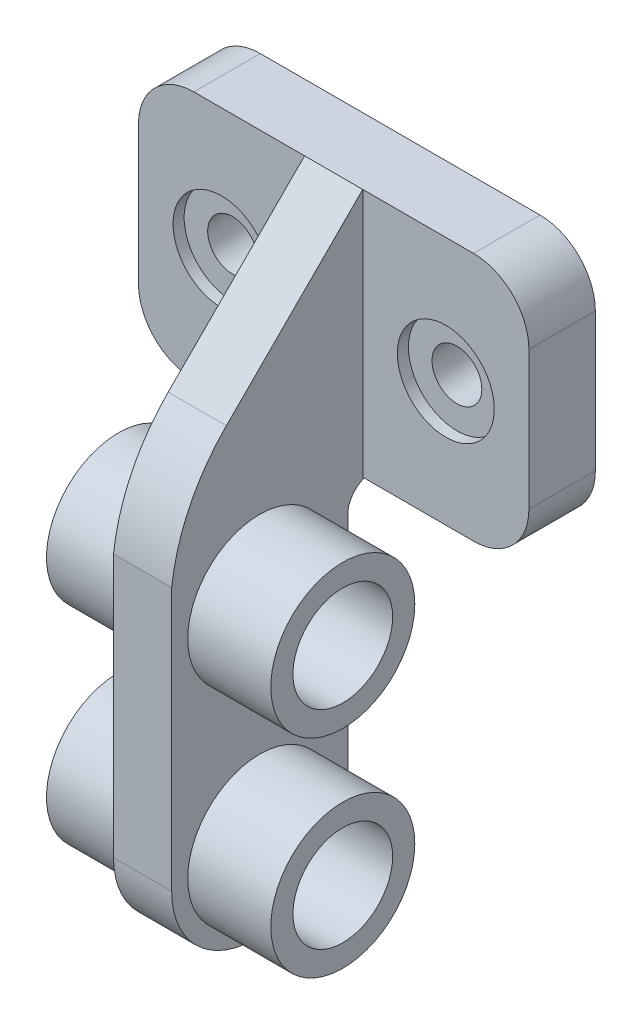
SolidWorks part; units mm, degrees
material "Oro puro"
ref_plane "Alzado" through (0, 0, 0) normal (0, 0, 1) x (1, 0, 0)
ref_plane "Planta" through (0, 0, 0) normal (0, 1, 0) x (1, 0, 0)
ref_plane "Vista lateral" through (0, 0, 0) normal (1, 0, 0) x (0, 0, -1)
sketch "Croquis2" plane through (0, 0, 0) normal (0, 0, 1) x (1, 0, 0)
  line L1 (-70.5, 45) -> (70.5, 45)
  line L2 (-70.5, 45) -> (-70.5, -45)
  line L3 (-70.5, -45) -> (70.5, -45)
  line L4 (70.5, 45) -> (70.5, -45)
  line L5 (-70.5, 45) -> (70.5, -45) construction
  line L6 (-70.5, -45) -> (70.5, 45) construction
  point P0 (0, 0)
  dimension "D1" = 141
  dimension "D2" = 90
extrude "Saliente-Extruir1" add sketch "Croquis2" along normal blind 24
fillet "Redondeo1" radius 20 4 edges at (70.5, -45, 12) (-70.5, -45, 12) (-70.5, 45, 12) (70.5, 45, 12)
sketch "Croquis3" plane through (0, 0, 24) normal (0, 0, 1) x (1, 0, 0)
  line L0 (-50.5, -45) -> (50.5, -45) construction
  line L1 (0, 45) -> (0, -45) construction
  line L2 (50.5, 45) -> (-50.5, 45) construction
  circle A0 centre (-40.5, 0) radius 17.5
  circle A1 centre (40.5, 0) radius 17.5
  dimension "D2" = 35
  dimension "D1" = 45
  dimension "D3" = 81
extrude "Cortar-Extruir1" cut sketch "Croquis3" against normal blind 4
sketch "Croquis5" plane through (0, 0, 24) normal (0, 0, 1) x (1, 0, 0)
  line L0 (-50.5, -45) -> (50.5, -45) construction
  line L1 (-10.5, 45) -> (10.5, 45)
  line L2 (-10.5, 45) -> (-10.5, -45)
  line L3 (-10.5, -45) -> (10.5, -45)
  line L4 (10.5, 45) -> (10.5, -45)
  line L5 (-10.5, 45) -> (10.5, -45) construction
  line L6 (-10.5, -45) -> (10.5, 45) construction
  point P0 (0, 0)
  dimension "D1" = 21
extrude "Saliente-Extruir2" add sketch "Croquis5" along normal blind 69
chamfer "Chaflán1" distance 69 angle 45 1 edges at (0, 45, 93)
fillet "Redondeo4" radius 69 1 edges at (0, -24, 93)
sketch "Croquis9" plane through (0, 0, 24) normal (0, 0, 1) x (1, 0, 0)
  line L0 (0, 0) -> (70.5, 0) construction
  line L1 (70.5, -25) -> (70.5, 25) construction
  line L2 (40.5, 0) -> (40.5, -151.9009) construction
sketch "Croquis10" plane through (0, -45, 0) normal (0, -1, 0) x (-1, 0, 0)
  line L1 (-10.5, -93) -> (10.5, -93)
  line L2 (-10.5, -93) -> (-10.5, -29.4105)
  line L3 (-10.5, -29.4105) -> (10.5, -29.4105)
  line L4 (10.5, -93) -> (10.5, -29.4105)
extrude "Saliente-Extruir6" add sketch "Croquis10" along normal blind 125
fillet "Redondeo6" radius 9 1 edges at (0, -45, 29.4105)
sketch "Croquis11" plane through (10.5, 0, 0) normal (1, 0, 0) x (0, 0, -1)
  line L0 (-93, -170) -> (-93, -45) construction
  line L2 (-29.4105, -64) -> (-93, -64) construction
  line L3 (-29.4105, -170) -> (-29.4105, -54) construction
  circle A2 centre (-61.2052, -64) radius 26
  circle A3 centre (-61.2052, -139) radius 26
  dimension "D1" = 64
  dimension "D4" = 75
  dimension "D2" = 52
  dimension "D3" = 52
fillet "Redondeo7" radius 30 2 edges at (0, -170, 29.4105) (0, -170, 93)
extrude "Saliente-Extruir8" add sketch "Croquis11" along normal blind 30 and the other way blind 51
sketch "Croquis15" plane through (40.5, 0, 0) normal (1, 0, 0) x (0, 0, -1)
  line L0 (-61.2052, -38) -> (-61.2052, -90) construction
  line L1 (-35.2052, -64) -> (-87.2052, -64) construction
  circle A0 centre (-61.2052, -64) radius 26 construction
  circle A1 centre (-61.2052, -64) radius 18
  dimension "D1" = 36
extrude "Cortar-Extruir3" cut sketch "Croquis15" against normal through all
sketch "Croquis16" plane through (40.5, 0, 0) normal (1, 0, 0) x (0, 0, -1)
  line L0 (-61.2052, -113) -> (-61.2052, -165) construction
  line L1 (-35.2052, -139) -> (-87.2052, -139) construction
  circle A0 centre (-61.2052, -139) radius 26 construction
  circle A1 centre (-61.2052, -139) radius 18
  dimension "D1" = 36
extrude "Cortar-Extruir4" cut sketch "Croquis16" against normal through all
sketch "Croquis17" plane through (0, 0, 20) normal (0, 0, 1) x (1, 0, 0)
  circle A0 centre (40.5, 0) radius 9
  point P0 (40.5, 0)
  dimension "D1" = 18
extrude "Cortar-Extruir5" cut sketch "Croquis17" against normal blind 30
sketch "Croquis18" plane through (0, 0, 20) normal (0, 0, 1) x (1, 0, 0)
  circle A0 centre (-40.5, 0) radius 9
  point P0 (-40.5, 0)
  dimension "D1" = 18
extrude "Cortar-Extruir6" cut sketch "Croquis18" against normal blind 30
